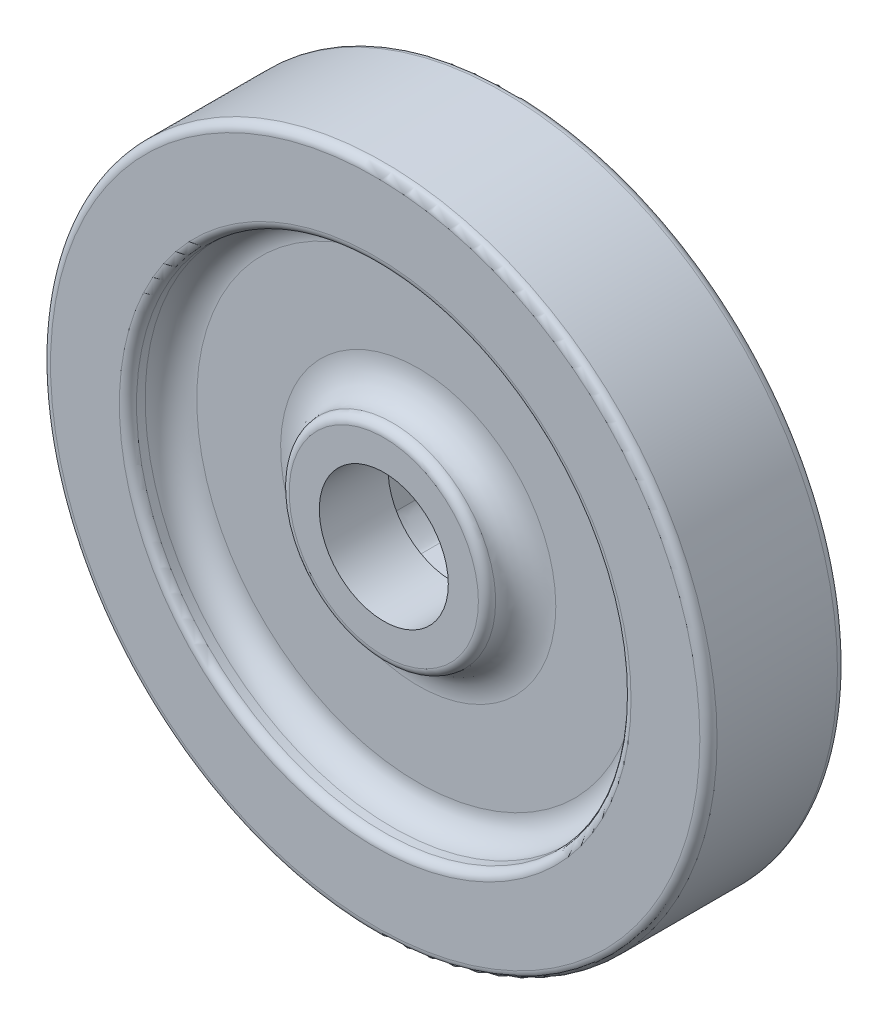
SolidWorks part; units mm, degrees
ref_plane "Front" through (0, 0, 0) normal (0, 0, 1) x (1, 0, 0)
ref_plane "Top" through (0, 0, 0) normal (0, 1, 0) x (1, 0, 0)
ref_plane "Right" through (0, 0, 0) normal (1, 0, 0) x (0, 0, -1)
ref_axis "Axis1" through (0, 0, 50) along (0, 0, -1)
sketch "Sketch1" plane through (0, 0, 0) normal (0, 1, 0) x (1, 0, 0)
  line L0 (9.525, 8.89) -> (15.24, 8.89)
  line L1 (15.24, 8.89) -> (15.24, 3.81)
  line L2 (15.24, 3.81) -> (36.5125, 3.81)
  line L3 (36.5125, 3.81) -> (36.5125, 10.16)
  line L4 (36.5125, 10.16) -> (49.2125, 10.16)
  line L5 (49.2125, 10.16) -> (49.2125, 0)
  line L6 (49.2125, 0) -> (9.525, 0)
  line L7 (9.525, 0) -> (9.525, 8.89)
  dimension "D1" = 9.525
  dimension "D2" = 49.2125
  dimension "D3" = 10.16
  dimension "D4" = 8.89
  dimension "D5" = 3.81
  dimension "D6" = 21.2725
  dimension "D7" = 5.715
revolve "Revolve1" add sketch "Sketch1" angle 360 about axis through (0, 0, 50) along (0, 0, -1)
fillet "Fillet1" radius 3.81 1 edges at (15.24, 0, -3.81)
fillet "Fillet2" radius 1.27 3 edges at (15.24, 0, -8.89) (36.5125, 0, -10.16) (49.2125, 0, -10.16)
fillet "Fillet3" radius 3.81 1 edges at (36.5125, 0, -3.81)
mirror "Mirror1" of "Fillet1", "Fillet2", "Fillet3", "Revolve1"
sketch "Sketch3" [suppressed] plane through (0, 0, -10.16) normal (0, 0, 1) x (1, 0, 0)
  arc A0 (-33.1205, 25.6803) -> (33.1205, 25.6803) centre (0, 0) cw construction
  arc A1 (33.1205, -25.6803) -> (-33.1205, -25.6803) centre (0, 0) cw construction
  text T0 "<b>800 - 3 7/8</b>" font "Century Gothic" height 3.81
  text T1 "<b>BB BaneBots</b>" font "Century Gothic" height 3.81
  point P7 (0, -41.91)
  point P8 (0, 41.91)
  dimension "D1" = 41.91
extrude "Boss-Extrude1" [suppressed] add sketch "Sketch3" against normal blind 1.27
sketch "Sketch4" [suppressed] plane through (0, 0, 10.16) normal (0, 0, 1) x (1, 0, 0)
  arc A0 (-33.1205, -25.6803) -> (33.1205, -25.6803) centre (0, 0) ccw construction
  arc A1 (33.1205, 25.6803) -> (-33.1205, 25.6803) centre (0, 0) ccw construction
  arc A2 (-33.1205, -25.6803) -> (33.1205, -25.6803) centre (0, 0) ccw construction
  arc A3 (33.1205, 25.6803) -> (-33.1205, 25.6803) centre (0, 0) ccw construction
  text T0 "<b>800 - 3 7/8</b>" font "Century Gothic" height 3.81
  text T1 "<b>BB BaneBots</b>" font "Century Gothic" height 3.81
extrude "Boss-Extrude2" [suppressed] add sketch "Sketch4" along normal blind 1.27
sketch "Sketch2" plane through (0, 0, -8.89) normal (0, 0, -1) x (-1, 0, 0)
  line L1 (10.16, 10.16) -> (-10.16, 10.16)
  line L2 (10.16, 10.16) -> (10.16, -10.16)
  line L3 (10.16, -10.16) -> (-10.16, -10.16)
  line L4 (-10.16, 10.16) -> (-10.16, -10.16)
  line L5 (10.16, 10.16) -> (-10.16, -10.16) construction
  line L6 (10.16, -10.16) -> (-10.16, 10.16) construction
  point P0 (0, 0)
  dimension "D1" = 20.32
extrude "Cut-Extrude1" cut sketch "Sketch2" against normal blind 7.62
fillet "Fillet4" radius 3.6532 4 edges at (-10.16, 10.16, -5.0479) (10.16, 10.16, -5.0479) (10.16, -10.16, -5.0479) (-10.16, -10.16, -5.0479)
